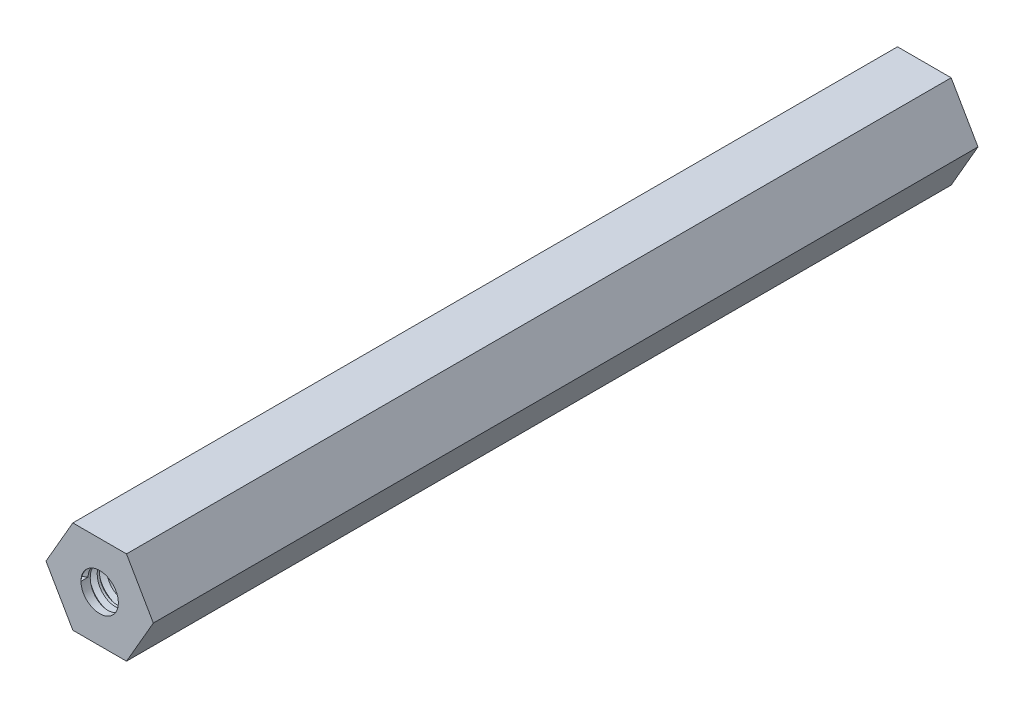
SolidWorks part; units mm, degrees
material "7075-T6 (SN)"
ref_plane "Alzado" through (0, 0, 0) normal (0, 0, 1) x (1, 0, 0)
ref_plane "Planta" through (0, 0, 0) normal (0, 1, 0) x (1, 0, 0)
ref_plane "Vista lateral" through (0, 0, 0) normal (1, 0, 0) x (0, 0, -1)
sketch "Croquis2" plane through (0, 0, 0) normal (0, 0, 1) x (1, 0, 0)
  line L1 (3.6662, -6.35) -> (7.3323, 0)
  line L2 (7.3323, 0) -> (3.6662, 6.35)
  line L3 (3.6662, 6.35) -> (-3.6662, 6.35)
  line L4 (-3.6662, 6.35) -> (-7.3323, 0)
  line L5 (-7.3323, 0) -> (-3.6662, -6.35)
  line L6 (-3.6662, -6.35) -> (3.6662, -6.35)
  circle A0 centre (0, 0) radius 6.35 construction
  dimension "D1" = 12.7
extrude "Extrusión Hex Profile" add sketch "Croquis2" along normal mid plane 112.671
sketch "Croquis3" plane through (0, 0, 0) normal (0, 0, 1) x (1, 0, 0)
  circle A0 centre (0, 0) radius 2.5527
  dimension "D1" = 5.1054
extrude "Tap Hole 1" cut sketch "Croquis3" against normal blind 19.05 from surface starting at face at (0, 0, 56.3355)
extrude "Tap Hole 2" cut sketch "Croquis3<3>" along normal blind 19.05 from surface starting at face at (0, 0, -56.3355)
sketch "Croquis3<3>" plane through (0, 0, 0) normal (0, 0, 1) x (1, 0, 0) same geometry as "Croquis3"
sketch "Croquis7" plane through (0, 0, 0) normal (0, 0, 1) x (1, 0, 0)
  circle A0 centre (0, 0) radius 6.8707
  dimension "D1" = 13.7414
extrude "ThunderHex" [suppressed] cut sketch "Croquis7" against normal through all both and the other way through all flip side to cut
sketch "Croquis8" plane through (0, 0, 0) normal (0, 1, 0) x (1, 0, 0)
  line L0 (0, -56.3355) -> (-5.5563, -56.3355) construction
  line L1 (3.6662, -56.3355) -> (-3.6662, -56.3355) construction
  line L3 (0, -56.3355) -> (0, 0) construction
  line L4 (-5.5563, -56.3355) -> (-6.35, -55.5417)
  line L5 (-6.35, -55.5417) -> (-6.35, -54.748)
  line L6 (-6.35, -54.748) -> (-5.9055, -54.748)
  line L7 (-5.9055, -54.748) -> (-5.9055, -53.1605)
  line L8 (-5.9055, -53.1605) -> (-12.7, -53.1605)
  line L9 (-12.7, -53.1605) -> (-12.7, -56.3355)
  line L10 (-12.7, -56.3355) -> (-5.5563, -56.3355)
  line L11 (-3.6662, -56.3355) -> (-7.3323, -56.3355) construction
  dimension "D1" = 11.811
  dimension "D2" = 12.7
  dimension "D3" = 45
  dimension "D4" = 0.7937
  dimension "D6" = 0.7937
  dimension "D7" = 3.175
  dimension "D8" = 25.4
revolve "Retaining Ring 1" [suppressed] cut sketch "Croquis8" angle 360 about L3
sketch "Croquis9" plane through (0, 0, 0) normal (0, -1, 0) x (1, 0, 0)
  line L0 (0, -56.3355) -> (-5.5563, -56.3355) construction
  line L3 (0, -56.3355) -> (0, 0) construction
  line L4 (-5.5563, -56.3355) -> (-6.35, -55.5417)
  line L5 (-6.35, -55.5417) -> (-6.35, -54.748)
  line L6 (-6.35, -54.748) -> (-5.9055, -54.748)
  line L7 (-5.9055, -54.748) -> (-5.9055, -53.1605)
  line L8 (-5.9055, -53.1605) -> (-12.7, -53.1605)
  line L9 (-12.7, -53.1605) -> (-12.7, -56.3355)
  line L10 (-12.7, -56.3355) -> (-5.5563, -56.3355)
  line L12 (-3.6662, -56.3355) -> (3.6662, -56.3355) construction
  line L13 (-7.3323, -56.3355) -> (-3.6662, -56.3355) construction
  dimension "D1" = 11.811
  dimension "D2" = 12.7
  dimension "D3" = 45
  dimension "D4" = 0.7937
  dimension "D6" = 0.7937
  dimension "D7" = 3.175
  dimension "D8" = 25.4
revolve "Retaining Ring 2" [suppressed] cut sketch "Croquis9" angle 360 about L3
sketch "Croquis10" plane through (0, 0, 0) normal (0, 1, 0) x (1, 0, 0)
  line L0 (0, -56.3355) -> (0, 0) construction
  line L1 (3.6662, -56.3355) -> (-3.6662, -56.3355) construction
  line L2 (0, -56.3355) -> (-5.5563, -56.3355) construction
  line L3 (-3.6662, -56.3355) -> (-7.3323, -56.3355) construction
  line L4 (-5.5563, -56.3355) -> (-6.35, -55.5417)
  line L5 (-6.35, -55.5417) -> (-6.35, -48.3853)
  line L6 (-6.35, -48.3853) -> (-9.525, -48.3853)
  line L7 (-9.525, -48.3853) -> (-9.525, -56.3355)
  line L8 (-9.525, -56.3355) -> (-5.5563, -56.3355)
  dimension "D2" = 12.7
  dimension "D1" = 45
  dimension "D3" = 0.7937
  dimension "D4" = 7.9502
  dimension "D5" = 19.05
revolve "Round End 1" [suppressed] cut sketch "Croquis10" angle 360 about L0
sketch "Croquis12" plane through (0, 0, 0) normal (0, -1, 0) x (1, 0, 0)
  line L0 (0, -56.3355) -> (0, 0) construction
  line L2 (0, -56.3355) -> (-5.5562, -56.3355) construction
  line L4 (-5.5562, -56.3355) -> (-6.35, -55.5417)
  line L5 (-6.35, -55.5417) -> (-6.35, -48.3853)
  line L6 (-6.35, -48.3853) -> (-9.525, -48.3853)
  line L7 (-9.525, -48.3853) -> (-9.525, -56.3355)
  line L8 (-9.525, -56.3355) -> (-5.5562, -56.3355)
  line L9 (-3.6662, -56.3355) -> (3.6662, -56.3355) construction
  dimension "D1" = 45
  dimension "D3" = 0.7937
  dimension "D4" = 7.9502
  dimension "D2" = 12.7
  dimension "D5" = 19.05
revolve "Round End 2" [suppressed] cut sketch "Croquis12" angle 360 about L0
thread "Rosca1" pitch 1.27 method cut profile "Perfil de rosca1" start angle 0, offset 0, length 0, pitch 1.27, diameter 5.1054
ref_plane "Plano1" through (2.5527, 0, -56.3355) normal (0, -1, 0) x (1, 0, 0)
sketch "Perfil de rosca1" plane through (2.5527, 0, -56.3355) normal (0, -1, 0) x (1, 0, 0)
  line L0 (0, 0) -> (0, 1.27) construction
  line L1 (0, 0) -> (0.6874, 0.3969)
  line L2 (0.6874, 0.3969) -> (0.6874, 0.5556)
  line L3 (0.6874, 0.5556) -> (0, 0.9525)
  line L4 (0.6874, 0.4762) -> (0, 0.4762) construction
  line L11 (0, 0) -> (0, 0.9525)
  point P2 (0, 0)
  dimension "Pitch" = 1.27
  dimension "Profile_Angle" = 60
  dimension "Profile_Land" = 0.1588
  dimension "Profile_Height" = 0.6874
thread "Rosca2" pitch 1.27 method cut profile "Perfil de rosca2" start angle 0, offset 0, length 0, pitch 1.27, diameter 5.1054
ref_plane "Plano2" through (-2.5527, 0, 56.3355) normal (0, -1, 0) x (-1, 0, 0)
sketch "Perfil de rosca2" plane through (-2.5527, 0, 56.3355) normal (0, -1, 0) x (-1, 0, 0)
  line L0 (0, 0) -> (0, 1.27) construction
  line L1 (0, 0) -> (0.6874, 0.3969)
  line L2 (0.6874, 0.3969) -> (0.6874, 0.5556)
  line L3 (0.6874, 0.5556) -> (0, 0.9525)
  line L4 (0.6874, 0.4762) -> (0, 0.4762) construction
  line L11 (0, 0) -> (0, 0.9525)
  point P2 (0, 0)
  dimension "Pitch" = 1.27
  dimension "Profile_Angle" = 60
  dimension "Profile_Land" = 0.1588
  dimension "Profile_Height" = 0.6874
equation "\"HexOD\"= 0.5pulgadas"
equation "\"Largo\"= 4.43586614"
equation "\"D1@Croquis2\"=\"HexOD\""
equation "\"D1@Extrusión Hex Profile\" = \"Largo\""
equation "\"TapHole\"= IIF ( \"HexOD\" = 0.5pulgadas , 0.2010pulgadas , 0.190pulgadas )"
equation "\"D1@Croquis3\"=\"TapHole\""
equation "\"ProTapHole\"= 0.75pulgadas"
equation "\"D1@Tap Hole 1\" = \"ProTapHole\""
equation "\"D1@Tap Hole 2\" = \"ProTapHole\""
equation "\"ThunderHex\"= IIF ( \"HexOD\" = 0.5pulgadas , 0.541pulgadas , 0.4035pulgadas )"
equation "\"D1@Croquis7\"=\"ThunderHex\""
equation "\"D2@Croquis8\"=\"HexOD\""
equation "\"D1@Croquis8\"=if(\"HexOD\"=0.5pulgadas, 0.465pulgadas, 0.35pulgadas )"
equation "\"D2@Croquis9\"=\"HexOD\""
equation "\"D1@Croquis9\"=if(\"HexOD\"=0.5pulgadas, 0.465pulgadas, 0.35pulgadas )"
equation "\"D8@Croquis8\"=\"HexOD\"*2"
equation "\"D8@Croquis9\"=\"HexOD\"*2"
equation "\"D5@Croquis10\"=\"HexOD\"*1.5"
equation "\"D5@Croquis12\"=\"HexOD\"*1.5"
equation "\"D4@Croquis10\"=if( \"D2@Croquis10\"=<0.375, 0.28, 0.313)"
equation "\"D4@Croquis12\"=if( \"D2@Croquis10\"=<0.375, 0.28, 0.313)"
